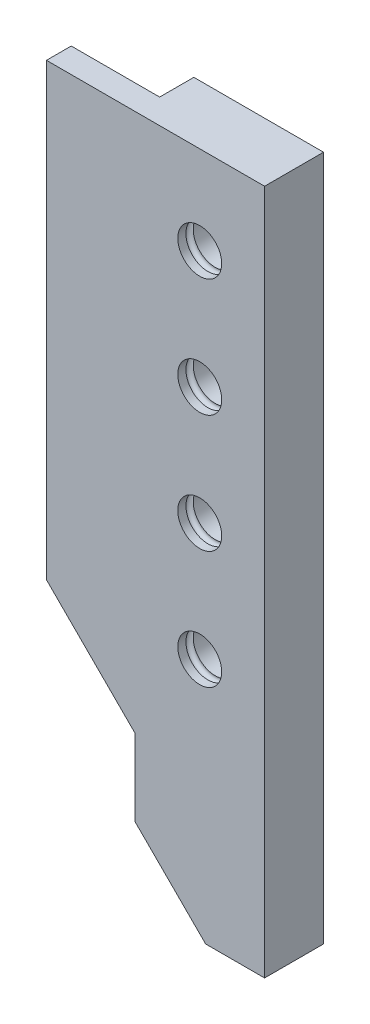
SolidWorks part; units mm, degrees
ref_plane "Front Plane" through (0, 0, 0) normal (0, 0, 1) x (1, 0, 0)
ref_plane "Top Plane" through (0, 0, 0) normal (0, 1, 0) x (1, 0, 0)
ref_plane "Right Plane" through (0, 0, 0) normal (1, 0, 0) x (0, 0, -1)
sketch "Sketch1" plane through (0, 0, 0) normal (0, 0, 1) x (1, 0, 0)
  line L0 (25.2, 31.3209) -> (25.2, -45)
  line L1 (25.2, -45) -> (40.2, -60)
  line L2 (40.2, -60) -> (40.2, 0) construction
  line L3 (40.2, -60) -> (40.2, -85)
  line L5 (62.2, -85) -> (62.2, 31.3209)
  line L6 (62.2, 31.3209) -> (25.2, 31.3209)
  line L12 (40.2, -85) -> (62.2, -85)
  line L13 (40.2, -60) -> (40.2, 31.3209)
  circle A0 centre (0, 0) radius 40.2 construction
  dimension "D1" = 80.4
  dimension "D2" = 15
  dimension "D3" = 15
  dimension "D4" = 60
  dimension "D5" = 25
  dimension "D6" = 22
extrude "Boss-Extrude1" add sketch "Sketch1" along normal blind 4.2 contours L1 L13 L6 L0 | L13 L3 L12 L5 L6 region at (32.9237, -10.7014, 0) region at (51.2, -26.8395, 0)
extrude "Boss-Extrude2" add sketch "Sketch1<3>" against normal blind 5.8 contours L13 L3 L12 L5 L6 region at (51.2, -26.8395, 0)
sketch "Sketch1<3>" plane through (0, 0, 0) normal (0, 0, 1) x (1, 0, 0) same geometry as "Sketch1"
sketch "Sketch2" plane through (0, 0, 4.2) normal (0, 0, 1) x (1, 0, 0)
  line L1 (40.2, -85) -> (62.2, -85) construction
  line L2 (62.2, 31.3209) -> (25.2, 31.3209) construction
  circle A0 centre (51.2, 16.3209) radius 3.725
  point P5 (51.2, -85)
  dimension "D1" = 7.45
  dimension "D2" = 15
extrude "Cut-Extrude1" cut sketch "Sketch2" against normal up to next
ref_axis "Axis1" through (51.2, 16.3209, -5.8) along (0, 0, 1)
ref_plane "Plane1" through (51.2, 0, 0) normal (-1, 0, 0) x (0, 0, 1)
sketch "Sketch3" plane through (51.2, 0, 0) normal (-1, 0, 0) x (0, 0, 1)
  line L0 (4.2, 31.3209) -> (4.2, -45) construction
  line L1 (-5.8, -85) -> (-5.8, 31.3209) construction
  circle A0 centre (-3.8, 20.2459) radius 0.65
  circle A1 centre (2.2, 20.2459) radius 0.65
  dimension "D1" = 1.3
  dimension "D3" = 2
  dimension "D4" = 2
  dimension "D2" = 0.2
revolve "Cut-Revolve1" cut sketch "Sketch3" angle 360 about axis through (51.2, 16.3209, -5.8) along (0, 0, 1)
pattern_linear "LPattern1" count 4 spacing 20 along (0, -1, 0) of "Cut-Extrude1", "Cut-Revolve1"
sketch "Sketch4" plane through (0, 0, 4.2) normal (0, 0, 1) x (1, 0, 0)
  line L0 (52.2, -85) -> (40.2, -73)
  line L1 (40.2, -85) -> (62.2, -85) construction
  line L2 (40.2, -85) -> (40.2, -60) construction
  line L3 (40.2, -73) -> (40.2, -85)
  line L4 (40.2, -85) -> (52.2, -85)
  dimension "D1" = 10
  dimension "D2" = 45
extrude "Cut-Extrude2" cut sketch "Sketch4" against normal up to next
